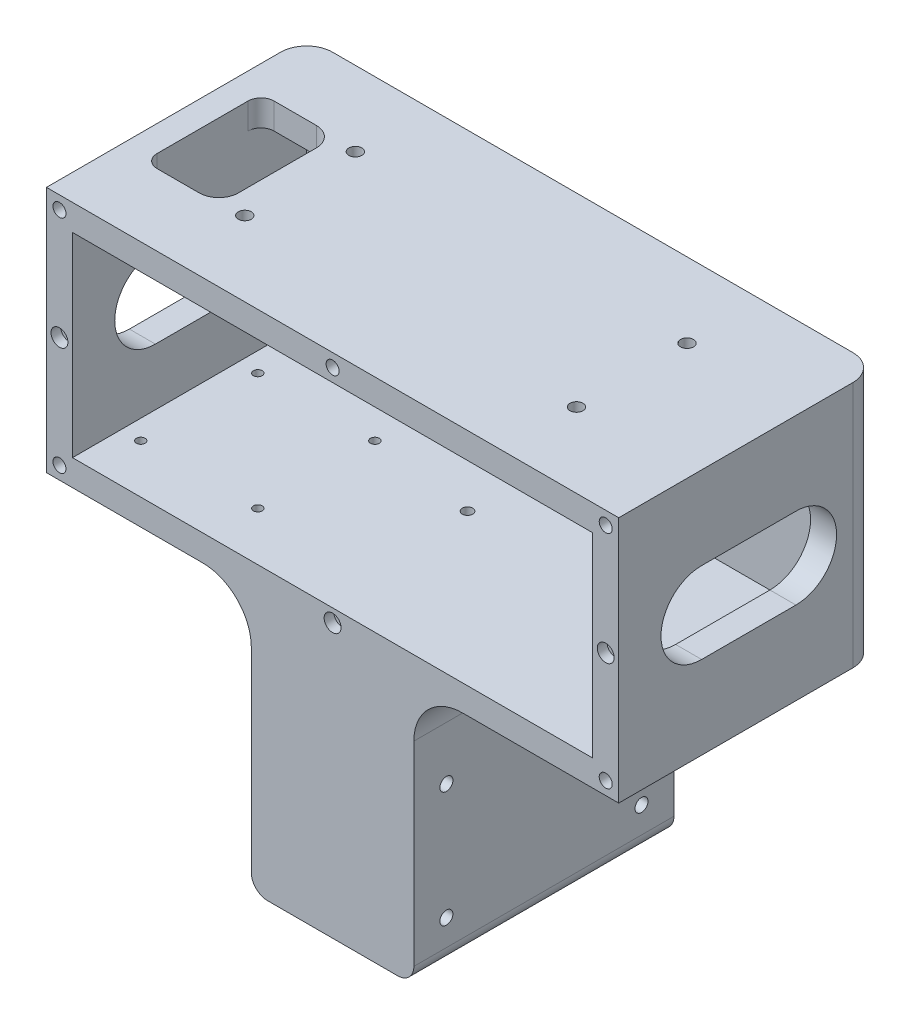
SolidWorks part; units mm, degrees
material "PETG-HF"
ref_plane "前视基准面" through (0, 0, 0) normal (0, 0, 1) x (1, 0, 0)
ref_plane "上视基准面" through (0, 0, 0) normal (0, 1, 0) x (1, 0, 0)
ref_plane "右视基准面" through (0, 0, 0) normal (1, 0, 0) x (0, 0, -1)
other "Configuration Table"
sketch "草图1" plane through (0, 0, 0) normal (0, 1, 0) x (1, 0, 0)
  line L1 (88, -40) -> (-88, -40)
  line L2 (88, -40) -> (88, 40)
  line L3 (88, 40) -> (-88, 40)
  line L4 (-88, -40) -> (-88, 40)
  line L5 (88, -40) -> (-88, 40) construction
  line L6 (88, 40) -> (-88, -40) construction
  point P0 (0, 0)
  dimension "D1" = 80
  dimension "D2" = 176
extrude "凸台-拉伸1" add sketch "草图1" along normal blind 76
sketch "草图3" plane through (0, 0, 40) normal (0, 0, 1) x (1, 0, 0)
  line L0 (-88, 0) -> (88, 0) construction
  line L1 (80, 8) -> (-80, 8)
  line L2 (80, 8) -> (80, 68)
  line L3 (80, 68) -> (-80, 68)
  line L4 (-80, 8) -> (-80, 68)
  line L5 (80, 8) -> (-80, 68) construction
  line L6 (80, 68) -> (-80, 8) construction
  line L7 (-88, 76) -> (-88, 0) construction
  line L8 (88, 76) -> (88, 0) construction
  line L9 (-88, 76) -> (88, 76) construction
  point P0 (0, 38)
  dimension "D1" = 8
  dimension "D2" = 8
  dimension "D3" = 8
  dimension "D4" = 8
extrude "切除-拉伸1" cut sketch "草图3" against normal offset from surface (72 mm away) 8 up to face at (0, 38, -40)
fillet "圆角1" radius 8 2 edges at (-88, 38, -40) (88, 38, -40)
sketch "草图5" plane through (0, 8, 0) normal (0, 1, 0) x (1, 0, 0)
  line L0 (-88, -40) -> (-88, 40) construction
  line L1 (-38, -25) -> (-74, -25) construction
  line L2 (-38, -25) -> (-38, 11) construction
  line L3 (-38, 11) -> (-74, 11) construction
  line L4 (-74, -25) -> (-74, 11) construction
  line L5 (-38, -25) -> (-74, 11) construction
  line L6 (-38, 11) -> (-74, -25) construction
  line L7 (-88, -40) -> (88, -40) construction
  line L8 (-74, -7) -> (-38, -7) construction
  line L9 (-56, -25) -> (-56, 11) construction
  circle A0 centre (-74, 11) radius 1.35
  circle A1 centre (-38, 11) radius 1.35
  circle A2 centre (-38, -25) radius 1.35
  circle A3 centre (-74, -25) radius 1.35
  point P0 (-56, -7)
  dimension "D4" = 2.7
  dimension "D1" = 14
  dimension "D2" = 36
  dimension "D3" = 36
  dimension "D5" = 15
extrude "切除-拉伸3" cut sketch "草图5" against normal through all
sketch "草图6" plane through (0, 76, 0) normal (0, 1, 0) x (1, 0, 0)
  line L0 (88, -40) -> (88, 32) construction
  line L1 (52, -17) -> (-50, -17) construction
  line L2 (52, -17) -> (52, 17) construction
  line L3 (52, 17) -> (-50, 17) construction
  line L4 (-50, -17) -> (-50, 17) construction
  line L5 (52, -17) -> (-50, 17) construction
  line L6 (52, 17) -> (-50, -17) construction
  line L7 (-88, -40) -> (88, -40) construction
  line L8 (1, 17) -> (1, -17) construction
  line L9 (-50, 0) -> (52, 0) construction
  line L10 (80, 40) -> (-80, 40) construction
  line L11 (-63, -12) -> (-63, 12) construction
  line L12 (-69, -12) -> (-69, 12)
  line L13 (-57, -12) -> (-57, 12)
  line L14 (-88, 32) -> (-88, -40) construction
  line L15 (-63, -18) -> (-76, -18)
  line L16 (-63, -18) -> (-63, 18)
  line L17 (-63, 18) -> (-76, 18)
  line L18 (-80, -14) -> (-80, 14)
  circle A0 centre (-50, 17) radius 2
  circle A1 centre (52, 17) radius 2
  circle A2 centre (52, -17) radius 2
  circle A3 centre (-50, -17) radius 2
  arc A4 (-69, -12) -> (-57, -12) centre (-63, -12) ccw
  arc A5 (-57, 12) -> (-69, 12) centre (-63, 12) ccw
  arc A6 (-76, -18) -> (-80, -14) centre (-76, -14) cw
  arc A7 (-76, 18) -> (-80, 14) centre (-76, 14) ccw
  point P0 (1, 0)
  point P20 (-63, 0)
  point P29 (-63, 18)
  point P30 (-63, -18)
  dimension "D4" = 4
  dimension "D10" = 4
  dimension "D1" = 36
  dimension "D2" = 34
  dimension "D3" = 102
  dimension "D5" = 13
  dimension "D6" = 12
  dimension "D7" = 22
  dimension "D8" = 22
  dimension "D9" = 8
extrude "切除-拉伸4" cut sketch "草图6" against normal up to surface (8 mm away) contours L17 A7 L18 A6 L15 A4 L12 A5 | L16 A5 L12 A4 | L13 A5 L16 A4 | A0 | A3 | A1 | A2 region at (-74.1606, 76, 0) region at (-65.8721, 76, 0) region at (-60.1279, 76, 0) region at (-50, 76, -17) region at (52, 76, -17) region at (52, 76, 17) region at (-50, 76, 17) up to face at (0, 68, 4)
sketch "草图7" plane through (0, 8, 0) normal (0, 1, 0) x (1, 0, 0)
  line L0 (70, 23) -> (70, -10) construction
  line L2 (88, -40) -> (88, 32) construction
  line L3 (-88, -40) -> (88, -40) construction
  circle A0 centre (70, 23) radius 1.6
  circle A1 centre (70, -10) radius 1.6
  circle A2 centre (-5, 6.5) radius 1.6
  point P6 (70, 6.5)
  dimension "D1" = 3.2
  dimension "D2" = 3.2
  dimension "D3" = 3.2
  dimension "D4" = 33
  dimension "D5" = 75
  dimension "D6" = 18
  dimension "D7" = 30
extrude "切除-拉伸5" cut sketch "草图7" against normal through all
sketch "草图8" plane through (0, 0, 0) normal (0, -1, 0) x (1, 0, 0)
  line L0 (-56, 25) -> (-56, -11) construction
  line L3 (-74, 7) -> (-38, 7) construction
  circle A0 centre (-74, 25) radius 2.5
  circle A1 centre (-38, 25) radius 2.5
  circle A2 centre (-38, -11) radius 2.5
  circle A3 centre (-74, -11) radius 2.5
  circle A4 centre (-5, -6.5) radius 3
  circle A5 centre (70, 10) radius 3
  circle A6 centre (70, -23) radius 3
  dimension "D1" = 5
  dimension "D2" = 6
  dimension "D3" = 6
  dimension "D4" = 6
extrude "切除-拉伸6" cut sketch "草图8" against normal blind 4
sketch "草图10" plane through (0, 0, -40) normal (0, 0, -1) x (-1, 0, 0)
  line L0 (-80, 27) -> (80, 27) construction
  line L1 (-80, 76) -> (-80, 0) construction
  line L2 (80, 0) -> (80, 76) construction
  line L3 (-80, 0) -> (80, 0) construction
  text T0 "XUANWU" font "Georgia" height 22
  dimension "D1" = 27
extrude "切除-拉伸8" cut sketch "草图10" against normal blind 2
sketch "草图11" plane through (0, 0, 40) normal (0, 0, 1) x (1, 0, 0)
  line L0 (-88, 76) -> (88, 76) construction
  line L1 (-88, 76) -> (-88, 0) construction
  line L2 (88, 76) -> (88, 0) construction
  circle A0 centre (-84, 72) radius 2
  circle A1 centre (-84, 4) radius 2
  circle A2 centre (84, 4) radius 2
  circle A3 centre (84, 72) radius 2
  circle A4 centre (0, 72) radius 2
  circle A5 centre (-84, 38) radius 2.6
  circle A6 centre (0, 4) radius 2.6
  circle A7 centre (84, 38) radius 2.6
  point P27 (-88, 38)
  point P28 (0, 76)
  dimension "D1" = 4
  dimension "D4" = 5.2
  dimension "D6" = 4
  dimension "D5" = 4
  dimension "D8" = 4
  dimension "D10" = 4
  dimension "D2" = 4
  dimension "D3" = 4
  dimension "D11" = 4
  dimension "D12" = 4
extrude "切除-拉伸9" cut sketch "草图11" against normal blind 8 contours A4 | A0 | A3 | A1 | A2
extrude "切除-拉伸10" cut sketch "草图11<3>" against normal blind 3 contours A5 | A6 | A7 region at (-84, 38, 40)
sketch "草图11<3>" plane through (0, 0, 40) normal (0, 0, 1) x (1, 0, 0) same geometry as "草图11"
sketch "Sketch1" plane through (-88, 0, 0) normal (-1, 0, 0) x (0, 0, 1)
  line L0 (14.5, 38) -> (-14.5, 38) construction
  line L1 (14.5, 25.5) -> (-14.5, 25.5)
  line L2 (14.5, 50.5) -> (-14.5, 50.5)
  line L4 (40, 0) -> (-40, 0) construction
  line L5 (40, 76) -> (40, 0) construction
  arc A0 (14.5, 25.5) -> (14.5, 50.5) centre (14.5, 38) ccw
  arc A1 (-14.5, 50.5) -> (-14.5, 25.5) centre (-14.5, 38) ccw
  point P2 (0, 38)
  point P7 (40, 38)
  point P14 (0, 0)
  point P15 (27, 38)
  dimension "D1" = 25
  dimension "D3" = 13
extrude "Cut-Extrude1" cut sketch "Sketch1" against normal through all
sketch "Sketch2" plane through (0, 0, -40) normal (0, 0, -1) x (-1, 0, 0)
  line L0 (-80, 0) -> (80, 0) construction
  line L1 (-25, 0) -> (25, 0)
  line L2 (-25, 0) -> (-25, -80)
  line L3 (-25, -80) -> (25, -80)
  line L4 (25, 0) -> (25, -80)
  point P6 (0, 0)
  dimension "D1" = 50
  dimension "D2" = 80
extrude "Boss-Extrude1" add sketch "Sketch2" against normal up to surface (80 mm away) up to face at (-81.4, 38, 40)
fillet "Fillet1" radius 15 2 edges at (25, 0, 0) (-25, 0, 0)
fillet "Fillet2" radius 5 2 edges at (25, -80, 0) (-25, -80, 0)
sketch "草图4" plane through (-25, 0, 0) normal (-1, 0, 0) x (0, 0, 1)
  line L0 (40, 76) -> (40, 0) construction
  line L7 (40, -80) -> (-40, -80) construction
  line L9 (30, -67) -> (-30, -67) construction
  line L10 (30, -67) -> (30, -31.4) construction
  line L11 (30, -31.4) -> (-30, -31.4) construction
  line L13 (-30, -67) -> (-30, -31.4) construction
  line L14 (30, -67) -> (-30, -31.4) construction
  line L15 (30, -31.4) -> (-30, -67) construction
  line L19 (-40, 0) -> (-40, 76) construction
  line L22 (-30, -49.2) -> (30, -49.2) construction
  line L23 (0, -31.4) -> (0, -67) construction
  circle A8 centre (-30, -31.4) radius 2
  circle A9 centre (30, -31.4) radius 2
  circle A10 centre (30, -67) radius 2
  circle A11 centre (-30, -67) radius 2
  point P0 (0, -49.2)
  dimension "D5" = 4
  dimension "D1" = 13
  dimension "D2" = 10
  dimension "D3" = 10
  dimension "D4" = 35.6
extrude "切除-拉伸2" cut sketch "草图4" against normal blind 8
extrude "Cut-Extrude2" cut sketch "草图4<2>" along normal blind 8 from surface starting at face at (25, -45, 0)
sketch "草图4<2>" plane through (-25, 0, 0) normal (-1, 0, 0) x (0, 0, 1) same geometry as "草图4"
